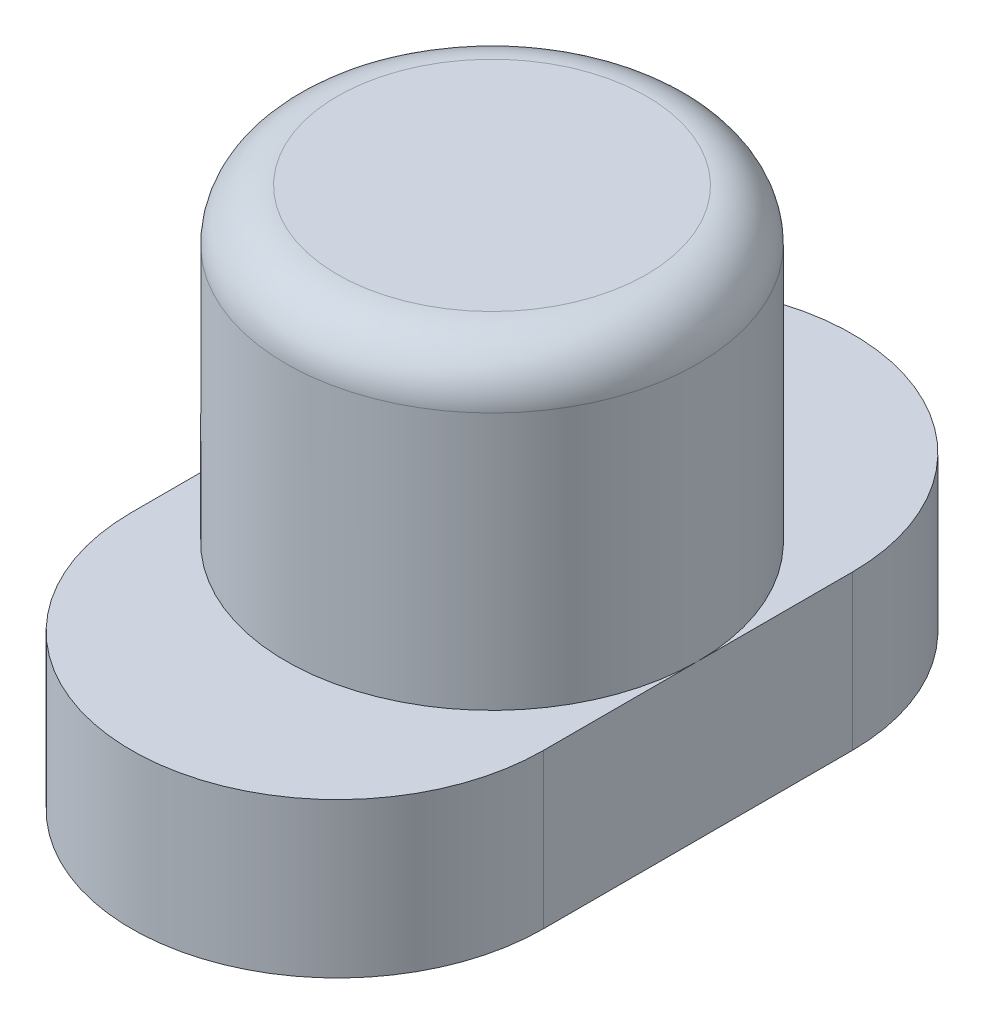
SolidWorks part; units mm, degrees
ref_plane "Front Plane" through (0, 0, 0) normal (0, 0, 1) x (1, 0, 0)
ref_plane "Top Plane" through (0, 0, 0) normal (0, 1, 0) x (1, 0, 0)
ref_plane "Right Plane" through (0, 0, 0) normal (1, 0, 0) x (0, 0, -1)
sketch "Sketch1" plane through (0, 0, 0) normal (0, 0, 1) x (1, 0, 0)
  line L1 (0, 9) -> (4, 9)
  line L2 (4, 9) -> (4, 3)
  line L3 (4, 3) -> (7, 3)
  line L4 (7, 3) -> (7, 0)
  line L6 (0, 9) -> (0, 6.9292) construction
  line L7 (0, 9) -> (0, 0)
  line L10 (0, 0) -> (7, 0)
  dimension "D1" = 4
  dimension "D2" = 3
  dimension "D3" = 6
  dimension "D4" = 3
revolve "Revolve1" add sketch "Sketch1" angle 360 about L6
sketch "Sketch2" plane through (0, 0, 0) normal (0, -1, 0) x (1, 0, 0)
  line L1 (-1.75, -1.25) -> (1.75, -1.25)
  line L2 (-1.75, -1.25) -> (-1.75, 1.25)
  line L3 (-1.75, 1.25) -> (1.75, 1.25)
  line L4 (1.75, -1.25) -> (1.75, 1.25)
  line L5 (-1.75, -1.25) -> (1.75, 1.25) construction
  line L6 (-1.75, 1.25) -> (1.75, -1.25) construction
  point P0 (0, 0)
  dimension "D1" = 3.5
  dimension "D2" = 2.5
extrude "Cut-Extrude1" cut sketch "Sketch2" against normal blind 3 draft 8 contours L3 L4 L1 L2
fillet "Fillet1" radius 1 1 edges at (-4, 9, 0)
sketch "Sketch3" plane through (0, 0, 0) normal (0, 1, 0) x (1, 0, 0)
  line L0 (0, -3) -> (0, 3) construction
  line L1 (-4, -3) -> (-4, 3)
  line L2 (4, -3) -> (4, 3)
  line L3 (0, 3) -> (0, 7) construction
  line L4 (-14, -3) -> (-14, 3)
  line L5 (14, -3) -> (14, 3)
  arc A1 (-4, -3) -> (4, -3) centre (0, -3) ccw
  arc A2 (4, 3) -> (-4, 3) centre (0, 3) ccw
  circle A3 centre (0, 0) radius 7 construction
  circle A4 centre (0, 0) radius 4 construction
  arc A5 (14, 3) -> (-14, 3) centre (0, 3) ccw
  arc A6 (-14, -3) -> (14, -3) centre (0, -3) ccw
  point P5 (0, 0)
  point P10 (5.3884, 0)
  point P11 (0, 0)
  point P14 (3.881, 3.119)
  point P23 (0, 0)
  dimension "D1" = 10
extrude "Cut-Extrude2" cut sketch "Sketch3" along normal through all
